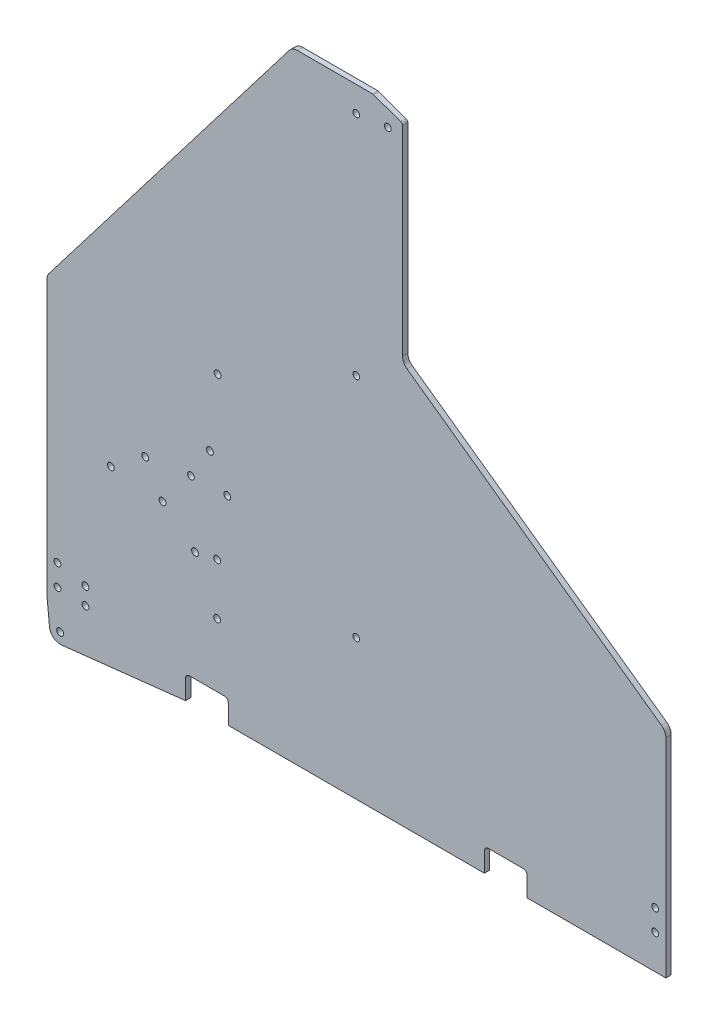
SolidWorks part; units mm, degrees
ref_plane "Front Plane" through (0, 0, 0) normal (0, 0, 1) x (1, 0, 0)
ref_plane "Top Plane" through (0, 0, 0) normal (0, 1, 0) x (1, 0, 0)
ref_plane "Right Plane" through (0, 0, 0) normal (1, 0, 0) x (0, 0, -1)
sketch "Sketch1" plane through (0, 0, 0) normal (0, 0, 1) x (1, 0, 0)
  line L0 (82.55, -20.32) -> (82.55, -6.35)
  line L2 (0, 0) -> (0, 157.48)
  line L4 (368.3, -20.32) -> (368.3, 106.68)
  line L5 (82.55, -6.35) -> (107.95, -6.35)
  line L6 (107.95, -6.35) -> (107.95, -20.32)
  line L7 (107.95, -20.32) -> (260.35, -20.32)
  line L8 (260.35, -20.32) -> (260.35, -6.35)
  line L9 (260.35, -6.35) -> (285.75, -6.35)
  line L10 (285.75, -6.35) -> (285.75, -20.32)
  line L11 (285.75, -20.32) -> (368.3, -20.32)
  line L12 (361.95, 12.7) -> (368.3, 12.7) construction
  line L13 (0, 0) -> (6.35, 0) construction
  line L14 (0.0315, -6.9818) -> (1.619, -22.8568)
  line L15 (8.6391, -28.5361) -> (82.55, -20.32)
  line L16 (0, 0) -> (0, -6.35)
  line L17 (85.725, 97.155) -> (82.9754, 95.5675) construction
  line L18 (97.0634, 115.6163) -> (58.5686, 93.3913) construction
  line L19 (97.0634, 115.6163) -> (107.3822, 97.7437) construction
  line L20 (58.5686, 93.3913) -> (68.8873, 75.5187) construction
  line L21 (107.3822, 97.7437) -> (68.8873, 75.5187) construction
  line L22 (97.0634, 115.6163) -> (68.8873, 75.5187) construction
  line L23 (58.5686, 93.3913) -> (107.3822, 97.7437) construction
  line L24 (7.9375, -22.225) -> (88.2169, 59.1366) construction
  line L25 (184.15, 62.98) -> (184.15, 197.98) construction
  line L26 (184.15, 197.98) -> (184.15, 332.98) construction
  line L27 (355.6, 335.28) -> (330.2, 335.28) construction
  line L28 (330.2, 335.28) -> (330.2, 220.98) construction
  line L29 (330.2, 220.98) -> (355.6, 220.98) construction
  line L30 (355.6, 220.98) -> (355.6, 335.28) construction
  line L31 (184.15, 347.98) -> (184.15, 269.4703) construction
  line L32 (12.7, 335.28) -> (38.1, 335.28) construction
  line L33 (38.1, 335.28) -> (38.1, 220.98) construction
  line L34 (12.7, 220.98) -> (12.7, 335.28) construction
  line L35 (38.1, 220.98) -> (12.7, 220.98) construction
  line L36 (194.15, 347.98) -> (211.6138, 341.63)
  line L37 (184.15, 347.98) -> (146.05, 347.98)
  line L38 (184.15, 347.98) -> (194.15, 347.98)
  line L39 (348.5362, 347.98) -> (413.4623, 347.98)
  line L40 (348.5362, 347.98) -> (211.6138, 347.98) construction
  line L42 (146.05, 347.98) -> (0, 157.48)
  line L44 (211.6138, 341.63) -> (211.6138, 218.44)
  line L45 (211.6138, 218.44) -> (368.3, 106.68)
  line L46 (194.15, 347.98) -> (-141.0713, 347.98) construction
  circle A0 centre (6.35, 0) radius 2.032
  circle A1 centre (6.35, 12.7) radius 2.032
  circle A2 centre (361.95, 0) radius 2.032
  circle A3 centre (361.95, 12.7) radius 2.032
  arc A5 (1.619, -22.8568) -> (8.6391, -28.5361) centre (7.9375, -22.225) ccw
  circle A6 centre (7.9375, -22.225) radius 2.032
  arc A7 (0, -6.35) -> (0.0315, -6.9818) centre (6.35, -6.35) ccw
  circle A8 centre (38.1, 78.105) radius 2.032
  circle A9 centre (85.725, 97.155) radius 2.032
  circle A10 centre (58.5686, 93.3913) radius 2.032
  circle A11 centre (68.8873, 75.5187) radius 2.032
  circle A12 centre (107.3822, 97.7437) radius 2.032
  circle A13 centre (97.0634, 115.6163) radius 2.032
  circle A14 centre (88.2169, 59.1366) radius 2.032
  circle A15 centre (184.15, 62.98) radius 2
  circle A16 centre (184.15, 197.98) radius 2
  circle A17 centre (184.15, 332.98) radius 2
  circle A18 centre (63.5, 316.23) radius 2.032
  circle A19 centre (101.6, 157.48) radius 2.032
  circle A20 centre (355.6, 335.28) radius 2.032
  circle A21 centre (330.2, 335.28) radius 2.032
  circle A22 centre (355.6, 220.98) radius 2.032
  circle A23 centre (330.2, 220.98) radius 2.032
  circle A24 centre (12.7, 335.28) radius 2.032
  circle A25 centre (38.1, 335.28) radius 2.032
  circle A26 centre (12.7, 220.98) radius 2.032
  circle A27 centre (38.1, 220.98) radius 2.032
  circle A28 centre (202.8819, 335.28) radius 2
  point P76 (0, 0)
  point P81 (0, 0)
  point P82 (184.15, 347.98)
  point P83 (202.8819, 344.805)
  dimension "D6" = 4.064
  dimension "D10" = 6.35
  dimension "D11" = 4.064
  dimension "D17" = 38.1
  dimension "D27" = 4
  dimension "D31" = 4.064
  dimension "D32" = 38.1
  dimension "D36" = 4.064
  dimension "D2" = 127
  dimension "D3" = 13.97
  dimension "D4" = 25.4
  dimension "D5" = 152.4
  dimension "D7" = 12.7
  dimension "D8" = 6.35
  dimension "D9" = 20.32
  dimension "D12" = 22.225
  dimension "D13" = 1.5875
  dimension "D14" = 82.55
  dimension "D15" = 368.3
  dimension "D16" = 6.35
  dimension "D18" = 98.425
  dimension "D19" = 47.625
  dimension "D20" = 19.05
  dimension "D21" = 3.175
  dimension "D22" = 60
  dimension "D23" = 20.6375
  dimension "D24" = 44.45
  dimension "D25" = 38.1
  dimension "D26" = 114.3
  dimension "D28" = 135
  dimension "D29" = 12.7
  dimension "D30" = 15
  dimension "D33" = 63.5
  dimension "D34" = 27.4638
  dimension "D35" = 101.6
  dimension "D37" = 114.3
  dimension "D38" = 25.4
  dimension "D39" = 12.7
  dimension "D40" = 157.48
  dimension "D41" = 129.54
  dimension "D42" = 368.3
  dimension "D43" = 10
  dimension "D44" = 6.35
  dimension "D45" = 31.75
  dimension "D46" = 6.35
extrude "Boss-Extrude1" add sketch "Sketch1" along normal blind 3.175 contours L16 A7 L14 A5 L15 L0 L5 L6 L7 L8 L9 L10 L11 L4 L42 L2 A19 A17 A16 A15 A14 A13 A12 A11 A10 A9 A8 A0 A1 A2 A3 A6 region at (168.2926, 118.3272, 0)
fillet "Fillet1" radius 2.286 4 edges at (285.75, -6.35, 1.5875) (107.95, -6.35, 1.5875) (260.35, -6.35, 1.5875) (82.55, -6.35, 1.5875)
fillet "Fillet2" radius 6.35 4 edges at (0, 157.48, 1.5875) (211.6138, 218.44, 1.5875) (368.3, 106.68, 1.5875) (146.05, 347.98, 1.5875)
sketch "Sketch2" plane through (0, 0, 0) normal (0, 0, -1) x (-1, 0, 0)
  circle A0 centre (-101.3398, 61.8475) radius 2.032 construction
  circle A1 centre (-101.3398, 31.3675) radius 2.032 construction
  circle A2 centre (-23.012, 8.964) radius 2.032 construction
  circle A3 centre (-23.012, -1.196) radius 2.032 construction
  circle A4 centre (-101.3398, 61.8475) radius 2.032
  circle A5 centre (-101.3398, 31.3675) radius 2.032
  circle A6 centre (-23.012, 8.964) radius 2.032
  circle A7 centre (-23.012, -1.196) radius 2.032
extrude "Cut-Extrude1" cut sketch "Sketch2" against normal through all
fillet "Fillet3" radius 1.5875 2 edges at (211.6138, 341.63, 1.5875) (194.15, 347.98, 1.5875)
